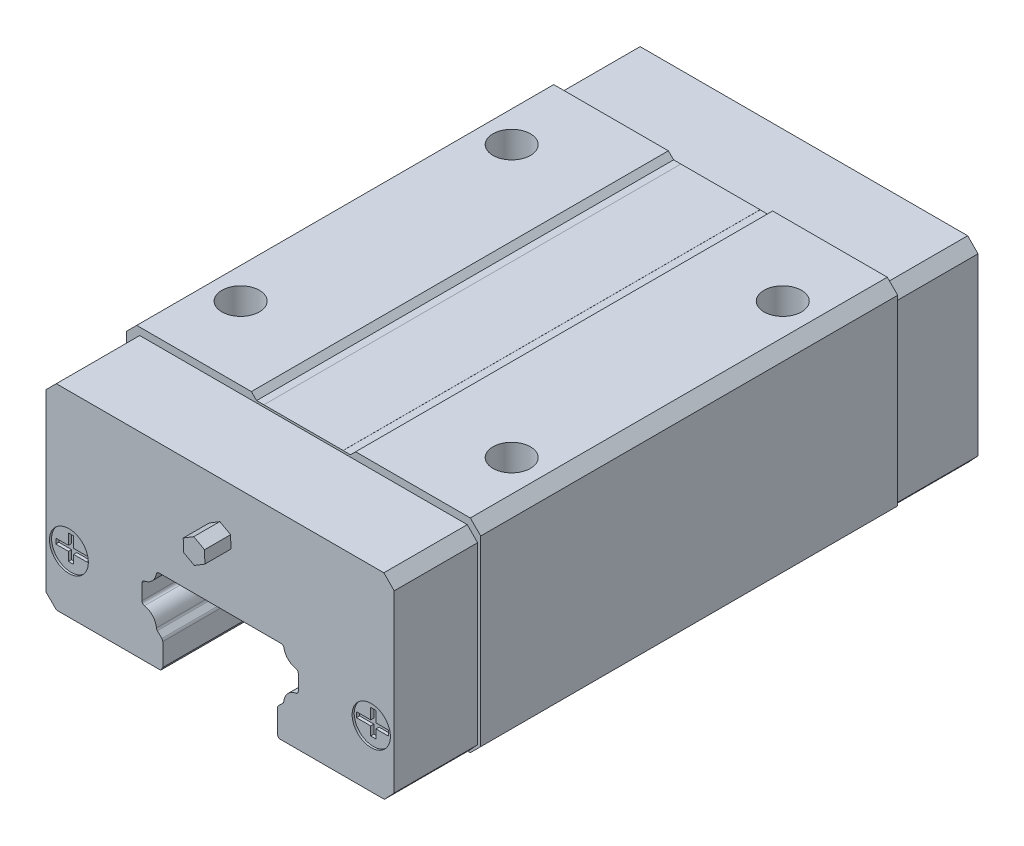
SolidWorks part; units mm, degrees
ref_plane "前视基准面" through (0, 0, 0) normal (0, 0, 1) x (1, 0, 0)
ref_plane "上视基准面" through (0, 0, 0) normal (0, 1, 0) x (1, 0, 0)
ref_plane "右视基准面" through (0, 0, 0) normal (1, 0, 0) x (0, 0, -1)
sketch "草图1" plane through (0, 0, 0) normal (0, 0, 1) x (1, 0, 0)
  line L0 (1190.2838, 451.8946) -> (1190.7838, 451.3946)
  line L1 (1191.4838, 451.3946) -> (1199.0818, 451.4024)
  line L2 (1189.4532, 440.3946) -> (1201.1143, 440.3946)
  line L3 (1199.0838, 451.3946) -> (1199.0818, 451.4024)
  line L6 (1178.5838, 433.3946) -> (1178.5838, 445.5946)
  line L17 (1179.5838, 432.3946) -> (1178.5838, 433.3946)
  line L30 (1179.5838, 432.3946) -> (1189.5838, 432.3946)
  line L89 (1189.7838, 432.7189) -> (1189.7838, 434.8766)
  line L94 (1189.6959, 435.0887) -> (1189.2646, 435.52)
  line L105 (1189.5838, 432.3946) -> (1189.6959, 432.5067)
  line L114 (1187.7838, 437.2641) -> (1187.7838, 438.7253)
  line L121 (1178.2838, 450.8946) -> (1179.2838, 451.8946)
  line L123 (1178.2838, 450.8946) -> (1178.2838, 445.8946)
  line L124 (1178.5838, 445.5946) -> (1178.2838, 445.8946)
  line L125 (1190.2838, 451.8946) -> (1179.2838, 451.8946)
  line L135 (1212.2838, 433.3946) -> (1212.2838, 450.8946)
  line L139 (1200.8716, 432.5067) -> (1200.9837, 432.3946)
  line L142 (1200.9837, 432.3946) -> (1211.2838, 432.3946)
  line L155 (1200.7838, 434.8766) -> (1200.7838, 432.7189)
  line L166 (1201.3029, 435.52) -> (1200.8716, 435.0887)
  line L178 (1202.7838, 438.7252) -> (1202.7838, 437.2639)
  line L190 (1212.2838, 433.3946) -> (1211.2838, 432.3946)
  line L264 (1211.2838, 451.8946) -> (1200.2838, 451.8946)
  line L269 (1191.4838, 451.3946) -> (1190.7838, 451.3946)
  line L270 (1199.7838, 451.3946) -> (1199.0838, 451.3946)
  line L273 (1199.7838, 451.3946) -> (1200.2838, 451.8946)
  line L281 (1211.2838, 451.8946) -> (1212.2838, 450.8946)
  circle A0 centre (1195.2838, 446.3946) radius 0.736
  arc A2 (1189.1781, 435.7032) -> (1188.0267, 436.9695) centre (1187.7548, 435.5656) ccw
  arc A3 (1189.6959, 432.5067) -> (1189.7838, 432.7189) centre (1189.4838, 432.7189) ccw
  arc A4 (1189.1781, 435.7032) -> (1189.2646, 435.52) centre (1189.4767, 435.7321) ccw
  arc A5 (1189.7838, 434.8766) -> (1189.6959, 435.0887) centre (1189.4838, 434.8766) ccw
  arc A14 (1189.4532, 440.3946) -> (1189.1587, 440.1517) centre (1189.4532, 440.0946) ccw
  arc A17 (1187.7838, 437.2641) -> (1188.0267, 436.9695) centre (1188.0838, 437.2641) ccw
  arc A18 (1188.0267, 439.0197) -> (1187.7838, 438.7253) centre (1188.0838, 438.7252) ccw
  arc A21 (1188.0267, 439.0197) -> (1189.1587, 440.1517) centre (1187.7548, 440.4236) ccw
  arc A22 (1201.4088, 440.1517) -> (1202.5408, 439.0197) centre (1202.8127, 440.4236) ccw
  arc A25 (1202.5408, 436.9695) -> (1201.3894, 435.7032) centre (1202.8127, 435.5656) ccw
  arc A28 (1201.3029, 435.52) -> (1201.3894, 435.7032) centre (1201.0908, 435.7321) ccw
  arc A32 (1200.7838, 432.7189) -> (1200.8716, 432.5067) centre (1201.0838, 432.7189) ccw
  arc A33 (1200.8716, 435.0887) -> (1200.7838, 434.8766) centre (1201.0838, 434.8766) ccw
  arc A34 (1201.4088, 440.1517) -> (1201.1143, 440.3946) centre (1201.1143, 440.0946) ccw
  arc A38 (1202.5408, 436.9695) -> (1202.7838, 437.2639) centre (1202.4838, 437.2641) ccw
  arc A41 (1202.7838, 438.7252) -> (1202.5408, 439.0197) centre (1202.4838, 438.7252) ccw
extrude "拉伸1" add sketch "草图1" along normal blind 40
sketch "草图2" plane through (0, 0, 40) normal (0, 0, 1) x (1, 0, 0)
  line L0 (1211.0414, 432.3946) -> (1200.9837, 432.3946)
  line L1 (1178.5838, 450.2047) -> (1178.5838, 433.3946)
  line L2 (1179.5737, 451.1946) -> (1210.9938, 451.1946)
  line L4 (1178.5838, 433.3946) -> (1179.5838, 432.3946)
  line L7 (1179.5838, 432.3946) -> (1189.5838, 432.3946)
  line L8 (1211.9838, 433.3946) -> (1211.9838, 450.8946)
  line L9 (1211.9838, 433.3946) -> (1211.9838, 450.1887)
  line L10 (1189.5838, 432.3946) -> (1189.7838, 432.7189)
  line L13 (1189.7838, 432.7189) -> (1189.7838, 434.8766)
  line L14 (1179.5737, 451.1946) -> (1178.5838, 450.2047)
  line L15 (1210.9938, 451.1946) -> (1211.9838, 450.1887)
  line L16 (1200.7838, 432.7189) -> (1200.7838, 434.8766)
  line L17 (1189.2646, 435.52) -> (1189.6959, 435.0887)
  line L18 (1200.8716, 435.0887) -> (1201.3029, 435.52)
  line L19 (1202.7838, 437.2639) -> (1202.7838, 438.7252)
  line L20 (1189.4532, 440.3946) -> (1201.1143, 440.3946)
  line L21 (1187.7838, 437.2641) -> (1187.7838, 438.7253)
  line L100 (1211.9838, 433.3946) -> (1211.0414, 432.3946)
  arc A0 (1200.9837, 432.3946) -> (1200.7838, 432.7189) centre (1201.1729, 432.7351) cw
  arc A1 (1200.7838, 434.8766) -> (1200.8716, 435.0887) centre (1201.0838, 434.8766) cw
  arc A2 (1201.3894, 435.7032) -> (1201.3029, 435.52) centre (1201.0912, 435.7319) cw
  arc A3 (1202.5408, 436.9695) -> (1201.3894, 435.7032) centre (1202.8118, 435.5665) ccw
  arc A4 (1202.7838, 437.2639) -> (1202.5408, 436.9695) centre (1202.4839, 437.2639) cw
  arc A5 (1202.7838, 438.7252) -> (1202.5408, 439.0197) centre (1202.4838, 438.7252) ccw
  arc A6 (1201.4088, 440.1517) -> (1202.5408, 439.0197) centre (1202.8127, 440.4236) ccw
  arc A7 (1201.1143, 440.3946) -> (1201.4088, 440.1517) centre (1201.1143, 440.0946) cw
  arc A8 (1189.4532, 440.3946) -> (1189.1587, 440.1517) centre (1189.4532, 440.0946) ccw
  arc A9 (1189.1587, 440.1517) -> (1188.0267, 439.0197) centre (1187.7548, 440.4236) cw
  arc A10 (1188.0267, 439.0197) -> (1187.7838, 438.7253) centre (1188.0838, 438.7252) ccw
  arc A11 (1187.7838, 437.2641) -> (1188.0267, 436.9695) centre (1188.0838, 437.2641) ccw
  arc A12 (1188.0267, 436.9695) -> (1189.1781, 435.7032) centre (1187.7548, 435.5656) cw
  arc A13 (1189.1781, 435.7032) -> (1189.2646, 435.52) centre (1189.4767, 435.7321) ccw
  arc A14 (1189.6959, 435.0887) -> (1189.7838, 434.8766) centre (1189.4838, 434.8766) cw
  circle A15 centre (1195.2838, 446.3946) radius 0.736
  dimension "D3" = 0.3
extrude "拉伸2" add sketch "草图2" along normal blind 8
ref_plane "基准面1" through (0, 0, 20) normal (0, 0, -1) x (-1, 0, 0)
mirror "镜向2" about plane through (0, 0, 20) normal (0, 0, -1) of "拉伸2"
sketch "草图3" plane through (0, 0, 48) normal (0, 0, 1) x (1, 0, 0)
  line L0 (1179.5838, 432.3946) -> (1189.5838, 432.3946) construction
  line L1 (1209.5328, 437.6446) -> (1209.5328, 436.8081)
  line L2 (1199.0818, 451.4024) -> (1191.4838, 451.3946) construction
  line L3 (1210.0328, 436.8292) -> (1210.0328, 436.8081)
  line L4 (1179.3204, 438.1446) -> (1180.5328, 438.1446)
  line L5 (1182.3926, 438.1446) -> (1182.3926, 437.6446)
  line L6 (1182.3926, 437.6446) -> (1181.0328, 437.6446)
  line L8 (1195.2828, 430.362) -> (1195.2828, 451.3985) construction
  line L9 (1180.5328, 439.1796) -> (1180.5328, 438.1446)
  line L10 (1180.5328, 439.1796) -> (1181.0328, 439.1796)
  line L11 (1181.0328, 439.1796) -> (1181.0328, 438.1446)
  line L12 (1181.0328, 436.8081) -> (1180.5328, 436.8081)
  line L14 (1179.3204, 438.1446) -> (1179.3204, 437.6446)
  line L15 (1211.2452, 438.1446) -> (1211.2452, 437.6446)
  line L16 (1208.1729, 438.1446) -> (1208.1729, 437.6446)
  line L17 (1211.2452, 438.1446) -> (1210.0328, 438.1446)
  line L18 (1208.1729, 437.6446) -> (1209.5328, 437.6446)
  line L19 (1209.5328, 436.8081) -> (1210.0328, 436.8081)
  line L20 (1210.0328, 439.1796) -> (1209.5328, 439.1796)
  line L21 (1210.0328, 439.1796) -> (1210.0328, 438.1446)
  line L22 (1209.5328, 439.1796) -> (1209.5328, 438.1446)
  line L23 (1209.5328, 438.1446) -> (1208.1729, 438.1446)
  line L24 (1210.0328, 437.6446) -> (1210.0328, 436.8292)
  line L25 (1210.0328, 437.6446) -> (1211.2452, 437.6446)
  line L26 (1181.0328, 438.1446) -> (1182.3926, 438.1446)
  line L27 (1180.5328, 437.6446) -> (1180.5328, 436.8081)
  line L28 (1181.0328, 437.6446) -> (1181.0328, 436.8081)
  line L29 (1180.5328, 437.6446) -> (1179.3204, 437.6446)
  circle A0 centre (1180.7828, 437.8946) radius 1.8636
  circle A1 centre (1209.7828, 437.8946) radius 1.8352
  circle A2 centre (1209.7828, 437.8946) radius 1.8636
  dimension "D2" = 5.5
  dimension "D4" = 0.5
  dimension "D5" = 0.5
extrude "拉伸3" cut sketch "草图3" against normal blind 0.2 contours A0 | A1
extrude "拉伸6" cut sketch "草图3<4>" against normal blind 0.5 contours L6 L28 L12 L27 L29 L14 L4 L9 L10 L11 L26 L5 | L25 L15 L17 L21 L20 L22 L23 L16 L18 L1 L19 L3 L24
sketch "草图3<4>" plane through (0, 0, 48) normal (0, 0, 1) x (1, 0, 0) same geometry as "草图3"
mirror "镜向3" about plane through (0, 0, 20) normal (0, 0, -1) of "拉伸3", "拉伸6"
sketch "草图5" plane through (0, 0, 48) normal (0, 0, 1) x (1, 0, 0)
  line L1 (1196.3212, 445.8289) -> (1196.2924, 447.0102)
  line L2 (1196.2924, 447.0102) -> (1195.2549, 447.5759)
  line L3 (1195.2549, 447.5759) -> (1194.2463, 446.9603)
  line L4 (1194.2463, 446.9603) -> (1194.2751, 445.779)
  line L5 (1194.2751, 445.779) -> (1195.3126, 445.2133)
  line L6 (1195.3126, 445.2133) -> (1196.3212, 445.8289)
  circle A0 centre (1195.2838, 446.3946) radius 1.0234 construction
extrude "拉伸7" add sketch "草图5" along normal blind 2.5
mirror "镜向4" about plane through (0, 0, 20) normal (0, 0, -1) of "拉伸7"
sketch "草图6" plane through (0, 451.8946, 0) normal (0, 1, 0) x (1, 0, 0)
  line L1 (1178.2838, -20) -> (1179.2838, -20) construction
  line L2 (1178.2838, -40) -> (1178.2838, 0) construction
  line L3 (1179.2838, -40) -> (1179.2838, 0) construction
  line L4 (1210.9543, -20) -> (1179.2838, -20) construction
  line L5 (10.725, -20) -> (-10.725, -20) construction
  line L6 (1195.2549, 8) -> (1195.2549, 6.0118) construction
  line L7 (1195.2549, -38.7793) -> (1195.2549, 6.0118) construction
  circle A0 centre (1208.2549, -7) radius 1.8
  circle A1 centre (1182.2549, -7) radius 1.8
  circle A2 centre (1208.2549, -33) radius 1.8
  circle A3 centre (1182.2549, -33) radius 1.8
  dimension "D1" = 3.6
  dimension "D2" = 13
  dimension "D3" = 13
extrude "拉伸8" cut sketch "草图6" against normal blind 10
